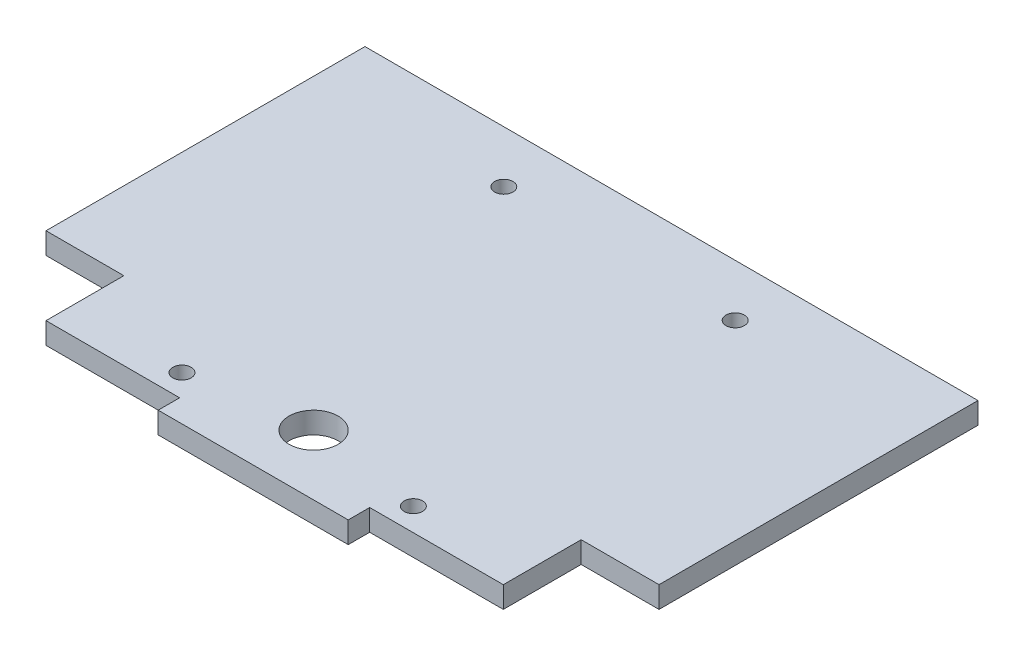
SolidWorks part; units mm, degrees
material "Maple"
ref_plane "Front Plane" through (0, 0, 0) normal (0, 0, 1) x (1, 0, 0)
ref_plane "Top Plane" through (0, 0, 0) normal (0, 1, 0) x (1, 0, 0)
ref_plane "Right Plane" through (0, 0, 0) normal (1, 0, 0) x (0, 0, -1)
sketch "Sketch1" plane through (0, 0, 0) normal (0, 1, 0) x (1, 0, 0)
  line L27 (0, 0) -> (0, 4.7)
  line L28 (-100, 25.4) -> (-100, 84.4686)
  line L29 (-100, 84.4686) -> (0, 84.4686)
  line L36 (-100, 25.4) -> (-74.6, 25.4)
  line L37 (-74.6, 0) -> (-74.6, 25.4)
  line L41 (0, 0) -> (-74.6, 0)
  line L42 (0, 20.7) -> (0, 84.4686)
  line L43 (0, 0) -> (-31, 0)
  line L44 (0, 0) -> (0, -7)
  line L45 (0, -7) -> (-31, -7)
  line L46 (-31, 0) -> (-31, -7)
  line L48 (-100, 84.4686) -> (0, 84.4686)
  line L49 (-100, 84.4686) -> (-100, 129.4686)
  line L50 (-100, 129.4686) -> (0, 129.4686)
  line L51 (0, 84.4686) -> (0, 129.4686)
  arc A1 (0, 4.7) -> (0, 20.7) centre (0, 12.7) cw
  dimension "D8" = 8
  dimension "D1" = 84.4686
  dimension "D3" = 25.4
  dimension "D4" = 100
  dimension "D5" = 7
  dimension "D9" = 19.7
  dimension "D10" = 45
extrude "Boss-Extrude1" add sketch "Sketch1" along normal blind 7 contours L29 L28 | L44 L43 L46 L45 | L49 L48 L51 L50 region at (-47.4836, 0, -45.094)
mirror "Mirror1" of "Boss-Extrude1"
sketch "Sketch2" plane through (0, 7, 0) normal (0, 1, 0) x (1, 0, 0)
  line L0 (-31, 0) -> (-74.6, 0) construction
  point P0 (37.75, 7.5)
  point P1 (-37.75, 7.5)
  point P2 (-37.75, 112.5)
  point P3 (37.75, 112.5)
  dimension "D1" = 105
  dimension "D2" = 75.5
  dimension "D3" = 37.75
  dimension "D4" = 7.5
hole_wizard "Ø6.0 (6) Diameter Hole1" positions "3DSketch1" profile "Sketch3" hole size "Ø6.0" standard "AS" end condition through all
sketch3d "3DSketch1"
  point P0 (-37.75, 7, -7.5)
  point P3 (37.75, 7, -7.5)
  point P6 (37.75, 7, -112.5)
  point P9 (-37.75, 7, -112.5)
sketch "Sketch3" plane through (-37.75, 7, -7.5) normal (1, 0, 0) x (0, 0, 1)
  line L0 (0, 0) -> (0, 7)
  line L1 (0, 7) -> (3, 7)
  line L2 (3, 7) -> (3, 0)
  line L5 (3, 0) -> (0, 0)
  line L11 (0, -6.35) -> (0, 107.95) construction
  dimension "Thru Hole Dia." = 6
  dimension "Thru Hole Depth" = 7
chamfer "Chamfer1" [suppressed] distance 20 angle 15
